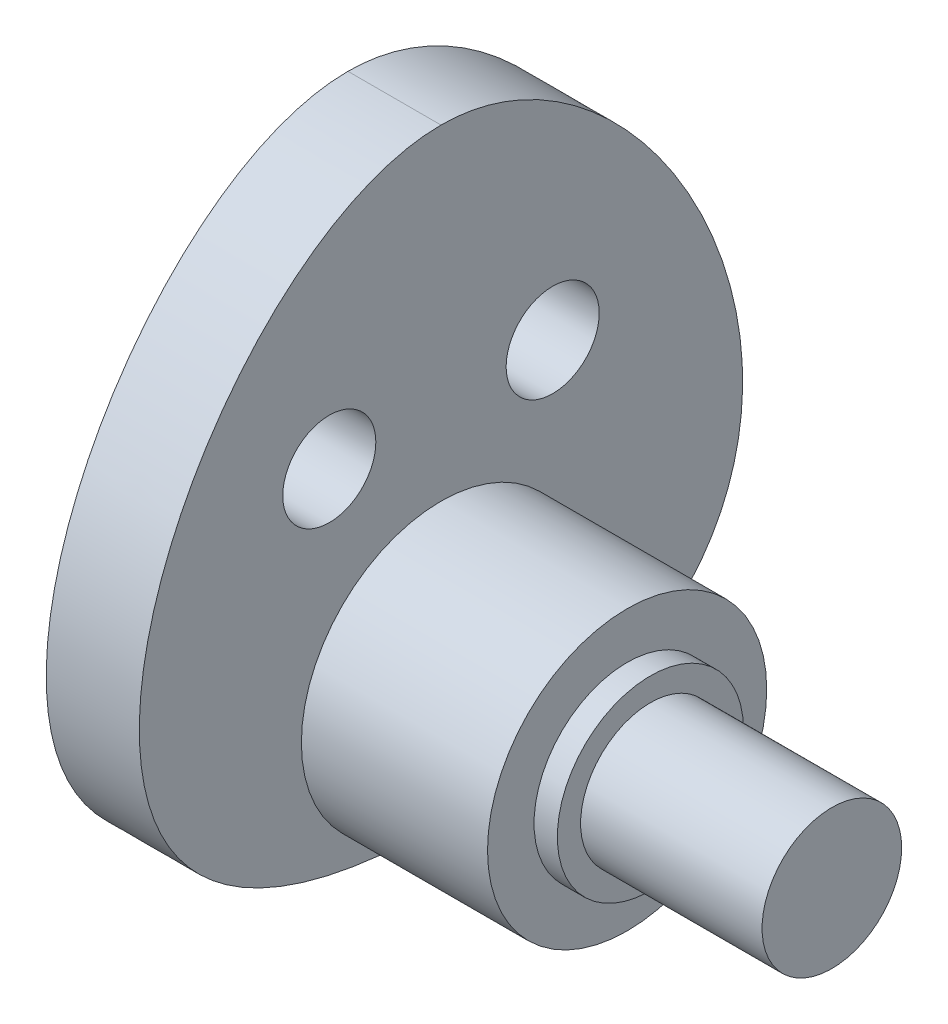
SolidWorks part; units mm, degrees
material "1060 Alloy"
ref_plane "Front Plane" through (0, 0, 0) normal (0, 0, 1) x (1, 0, 0)
ref_plane "Top Plane" through (0, 0, 0) normal (0, 1, 0) x (1, 0, 0)
ref_plane "Right Plane" through (0, 0, 0) normal (1, 0, 0) x (0, 0, -1)
sketch "Sketch1" plane through (0, 0, 0) normal (1, 0, 0) x (0, 0, -1)
  line L0 (0, 0) -> (0, -3) construction
  line L1 (0, 0) -> (-2, -3.4641) construction
  line L2 (0, 0) -> (-4.3301, -2.5) construction
  line L3 (0, 0) -> (-6, 0) construction
  line L4 (0, 0) -> (-6.0622, 3.5) construction
  line L5 (0, 0) -> (-4, 6.9282) construction
  line L6 (0, 0) -> (0, 10) construction
  circle A4 centre (0, 0) radius 2.5
  spline S0 degree 3 poles (0, 10) (-5.5754, 10) (-11.2568, -3) (0, -3) knots 0 0 0 0 1 1 1 1
  spline S1 degree 3 poles (0, 10) (5.5754, 10) (11.2568, -3) (0, -3) knots 0 0 0 0 1 1 1 1
  dimension "D2" = 10
  dimension "D4" = 5
  dimension "D5" = 3
  dimension "D6" = 4
  dimension "D7" = 5
  dimension "D8" = 6
  dimension "D9" = 7
  dimension "D10" = 8
  dimension "D11" = 30
  dimension "D12" = 30
  dimension "D13" = 30
  dimension "D14" = 30
  dimension "D15" = 30
extrude "Boss-Extrude1" add sketch "Sketch1" along normal blind 2
sketch "Sketch2" plane through (2, 0, 0) normal (1, 0, 0) x (0, 0, -1)
  circle A0 centre (0, 0) radius 3
  dimension "D2" = 6
extrude "Boss-Extrude2" add sketch "Sketch2" along normal blind 7.5
sketch "Sketch3" plane through (0, 0, 0) normal (-1, 0, 0) x (0, 0, 1)
  circle A1 centre (-2.4, 4.8) radius 1
  circle A2 centre (2.4, 4.8) radius 1
  dimension "D2" = 2
  dimension "D3" = 4.8
  dimension "D5" = 2.4
  dimension "D6" = 2.4
extrude "Cut-Extrude1" cut sketch "Sketch3" against normal up to next
chamfer "Chamfer1" distance 1 angle 45 1 edges at (2, 0, -2.5)
sketch "Sketch4" plane through (9.5, 0, 0) normal (1, 0, 0) x (0, 0, -1)
  circle A0 centre (0, 0) radius 1.5
  dimension "D1" = 3
extrude "Cut-Extrude2" cut sketch "Sketch4" against normal blind 3 flip side to cut
sketch "Sketch5" plane through (6.5, 0, 0) normal (1, 0, 0) x (0, 0, -1)
  circle A0 centre (0, 0) radius 2
  dimension "D1" = 4
extrude "Cut-Extrude3" cut sketch "Sketch5" against normal blind 0.5 flip side to cut
sketch "Sketch6" plane through (9.5, 0, 0) normal (1, 0, 0) x (0, 0, -1)
  circle A0 centre (0, 0) radius 1.5
extrude "Boss-Extrude3" add sketch "Sketch6" along normal blind 0.9
